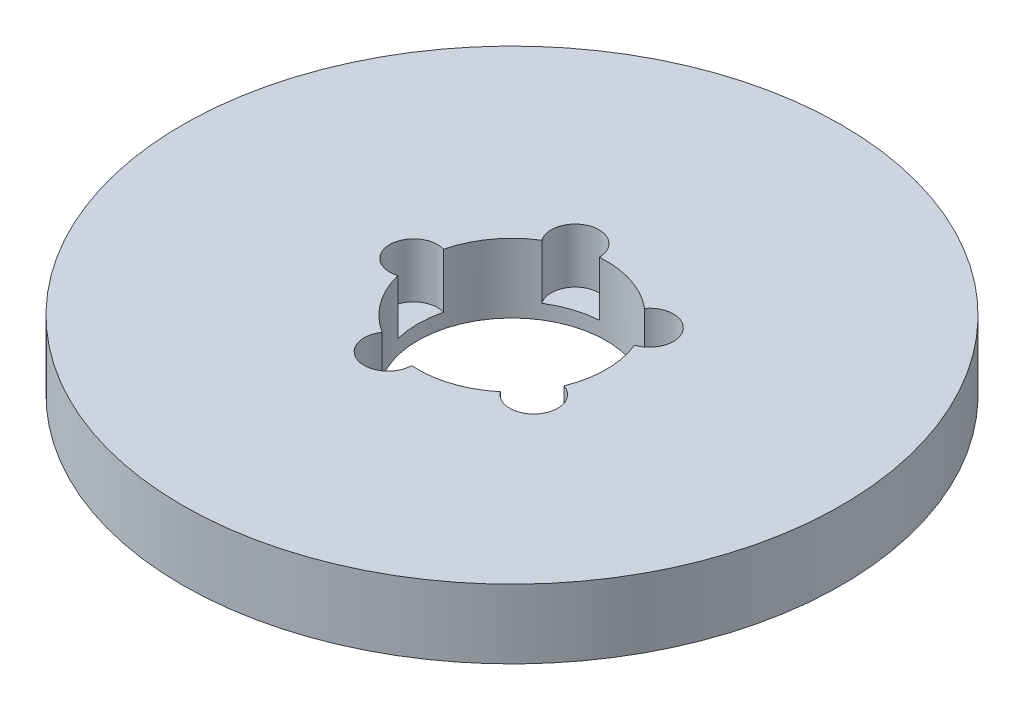
SolidWorks part; units mm, degrees
ref_plane "Front Plane" through (0, 0, 0) normal (0, 0, 1) x (1, 0, 0)
ref_plane "Top Plane" through (0, 0, 0) normal (0, 1, 0) x (1, 0, 0)
ref_plane "Right Plane" through (0, 0, 0) normal (1, 0, 0) x (0, 0, -1)
sketch "Sketch1" plane through (0, 0, 0) normal (0, 1, 0) x (1, 0, 0)
  circle A0 centre (0, 0) radius 52.5
  dimension "FLANGE_OD" = 105
extrude "Boss-Extrude1" add sketch "Sketch1" along normal blind 11
sketch "Sketch2" plane through (0, 0, 0) normal (0, 1, 0) x (1, 0, 0)
  circle A0 centre (0, 0) radius 15
  dimension "BORE_D" = 30
extrude "Cut-Extrude1" cut sketch "Sketch2" along normal through all
sketch "Sketch3" plane through (0, 11, 0) normal (0, 1, 0) x (1, 0, 0)
  circle A0 centre (0, 0) radius 15.6777 construction
  circle A1 centre (-15.6777, 0) radius 3.8087
  dimension "BOLT_D" = 7.6173
  dimension "BOLT_PCD" = 31.3554
extrude "Cut-Extrude2" cut sketch "Sketch3" against normal blind 8.6978
pattern_circular "CirPattern1" count 5 over 360 about axis through (0, 0, 0) along (0, 1, 0) of "Cut-Extrude2"
